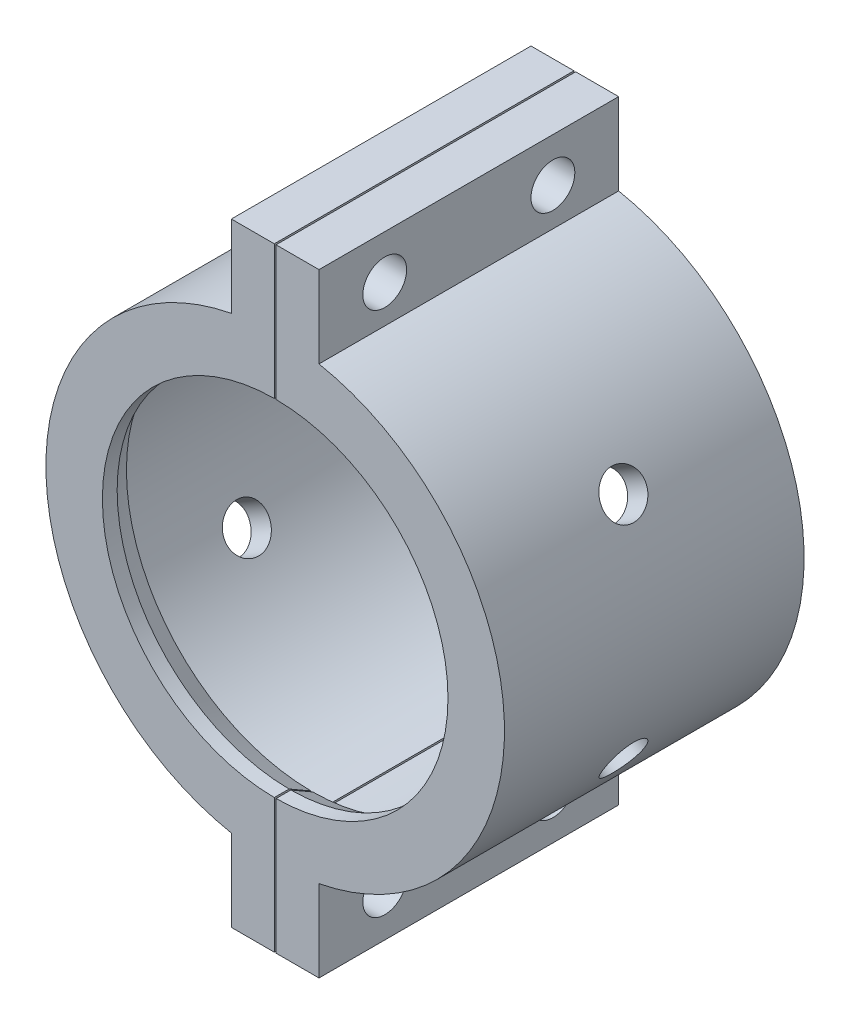
SolidWorks part; units mm, degrees
ref_plane "Front Plane" through (0, 0, 0) normal (0, 0, 1) x (1, 0, 0)
ref_plane "Top Plane" through (0, 0, 0) normal (0, 1, 0) x (1, 0, 0)
ref_plane "Right Plane" through (0, 0, 0) normal (1, 0, 0) x (0, 0, -1)
sketch "Sketch2" plane through (0, 0, 0) normal (0, 1, 0) x (1, 0, 0)
  line L0 (0, 0) -> (25.039, 0) construction
  line L1 (25.039, 0) -> (25.039, 2.14)
  line L2 (25.039, 2.14) -> (26.875, 5.32)
  line L3 (25.039, 2.14) -> (25.039, 5.32) construction
  line L4 (33.225, 5.32) -> (33.225, 0)
  line L5 (33.225, 0) -> (25.039, 0)
  line L6 (26.875, 5.32) -> (33.225, 5.32)
  line L7 (0, 0) -> (0, 46.1774) construction
  point P3 (0, 0)
  point P5 (0, 0)
  point P11 (0, 0)
  point P12 (0, 0)
  dimension "D2" = 26.875
  dimension "D3" = 5.32
  dimension "D4" = 3.18
  dimension "D5" = 6.35
  dimension "D6" = 30
revolve "Revolve1" add sketch "Sketch2" angle 360 about L7
sketch "Sketch8" plane through (0, 0, 0) normal (0, 1, 0) x (1, 0, 0)
  line L1 (-33.225, 5.32) -> (-33.225, 43.42)
  line L2 (-33.225, 43.42) -> (-29.845, 43.42)
  line L3 (-29.845, 43.42) -> (-29.845, 5.32)
  line L4 (33.225, 5.32) -> (-33.225, 5.32) construction
  line L5 (33.225, 5.32) -> (-33.225, 5.32) construction
  line L6 (-29.845, 5.32) -> (-33.225, 5.32)
  line L7 (0, 0) -> (0, 125.228) construction
  line L8 (-33.225, 0) -> (33.225, 0) construction
  dimension "D3" = 29.845
  dimension "D5" = 38.1
revolve "Revolve2" add sketch "Sketch8" angle 360 about L7
sketch "Sketch19" plane through (0, 0, 0) normal (0, 0, 1) x (1, 0, 0)
  line L0 (-6.35, 32.6125) -> (-6.35, 44.45)
  line L1 (6.35, -44.45) -> (-6.35, -44.45)
  line L2 (6.35, -44.45) -> (6.35, -32.6125)
  line L3 (6.35, 44.45) -> (-6.35, 44.45)
  line L4 (-6.35, -44.45) -> (-6.35, -32.6125)
  line L5 (6.35, -44.45) -> (-6.35, 44.45) construction
  line L6 (6.35, 44.45) -> (-6.35, -44.45) construction
  line L7 (6.35, 32.6125) -> (6.35, 44.45)
  circle A0 centre (0, 0) radius 33.225 construction
  arc A1 (-6.35, -32.6125) -> (6.35, -32.6125) centre (0, 0) ccw
  arc A2 (6.35, 32.6125) -> (-6.35, 32.6125) centre (0, 0) ccw
  dimension "D1" = 12.7
  dimension "D2" = 88.9
extrude "Boss-Extrude10" add sketch "Sketch19" against normal up to surface (43.42 mm away) up to face at (33.225, 0, -43.42)
sketch "Sketch18" plane through (0, 0, 0) normal (1, 0, 0) x (0, 0, -1)
  line L3 (43.42, 44.45) -> (0, 44.45) construction
  line L4 (0, -44.45) -> (0, -32.6125) construction
  line L5 (43.42, -32.6125) -> (43.42, -44.45) construction
  line L6 (43.42, -44.45) -> (0, -44.45) construction
  circle A0 centre (9.525, 38.1) radius 3.175
  circle A1 centre (33.895, 38.1) radius 3.175
  circle A2 centre (9.525, -38.1) radius 3.175
  circle A3 centre (33.895, -38.1) radius 3.175
  dimension "D1" = 6.35
  dimension "D2" = 6.35
  dimension "D3" = 9.525
  dimension "D4" = 9.525
  dimension "D5" = 6.35
extrude "Cut-Extrude7" cut sketch "Sketch18" against normal through all both and the other way through all
sketch "Sketch15" [suppressed] plane through (0, 0, -5.32) normal (0, 0, -1) x (-1, 0, 0)
  circle A1 centre (0, 0) radius 29.845
  circle A2 centre (0, 0) radius 29.845
  dimension "D1" = 0
sketch "Sketch21" plane through (0, 0, 0) normal (0, 0, 1) x (1, 0, 0)
  line L0 (0, 0) -> (0, 17.0984) construction
  line L1 (0, 0) -> (14.4923, 0) construction
  line L2 (0, 0) -> (14.7479, 8.5147) construction
  line L3 (-30.6026, 53.0053) -> (0, 0) construction
  line L4 (0, 0) -> (37.5938, 65.1143) construction
  dimension "D1" = 30
  dimension "D2" = 30
ref_axis "Axis4" through (0, 0, 3.175) along (0, 0, -1)
ref_plane "Plane1" through (0, 0, 0) normal (-0.866, -0.5, 0) x (-0.5, 0.866, 0)
sketch "Sketch23" plane through (0, 0, 0) normal (-0.866, -0.5, 0) x (-0.5, 0.866, 0)
  line L0 (0, -3.175) -> (0, 66.675) construction
  line L1 (0, 43.42) -> (0, 0) construction
  line L2 (33.225, 43.42) -> (-25.0683, 43.42) construction
  line L3 (-100000, 0) -> (100037.5938, 0) construction
  circle A0 centre (0, 21.71) radius 3.175
  point P13 (0, 21.71)
  dimension "D1" = 6.35
extrude "Cut-Extrude9" cut sketch "Sketch23" against normal through all both and the other way through all
mirror "Mirror3" about plane through (0, 0, 0) normal (0, 1, 0) of "Cut-Extrude9"
sketch "Sketch25" plane through (0, 0, 0) normal (0, 0, 1) x (1, 0, 0)
  line L1 (-0.127, -63.5) -> (0.127, -63.5)
  line L2 (-0.127, -63.5) -> (-0.127, 63.5)
  line L3 (-0.127, 63.5) -> (0.127, 63.5)
  line L4 (0.127, -63.5) -> (0.127, 63.5)
  line L5 (-0.127, -63.5) -> (0.127, 63.5) construction
  line L6 (-0.127, 63.5) -> (0.127, -63.5) construction
  point P0 (0, 0)
  dimension "D1" = 127
  dimension "D2" = 0.254
extrude "Cut-Extrude11" cut sketch "Sketch25" against normal through all both and the other way through all
extrude "Boss-Extrude6" [suppressed] add sketch "Sketch15" along normal up to surface (38.1 mm away)
sketch "Sketch12" [suppressed] plane through (0, 0, -63.5) normal (0, 0, -1) x (-1, 0, 0)
  line L1 (-12.7, 42.75) -> (12.7, 42.75)
  line L2 (-12.7, 42.75) -> (-12.7, 36.4)
  line L3 (-12.7, 36.4) -> (12.7, 36.4)
  line L4 (12.7, 42.75) -> (12.7, 36.4)
  line L5 (-12.7, 42.75) -> (12.7, 36.4) construction
  line L6 (-12.7, 36.4) -> (12.7, 42.75) construction
  circle A0 centre (0, 0) radius 39.575 construction
  point P0 (0, 39.575)
  dimension "D1" = 6.35
  dimension "D2" = 25.4
extrude "Boss-Extrude4" [suppressed] add sketch "Sketch12" against normal blind 25.4
sketch "Sketch11" [suppressed] plane through (0, 0, 0) normal (0, 1, 0) x (1, 0, 0)
  line L0 (29.845, 63.5) -> (-29.845, 63.5) construction
  line L1 (0, 44.4942) -> (5.461, 47.6471)
  line L2 (5.461, 47.6471) -> (5.461, 53.9529)
  line L3 (5.461, 53.9529) -> (0, 57.1058) construction
  line L4 (0, 57.1058) -> (-5.461, 53.9529) construction
  line L5 (-5.461, 53.9529) -> (-5.461, 47.6471)
  line L6 (-5.461, 47.6471) -> (0, 44.4942)
  line L7 (-5.461, 53.9529) -> (-5.715, 63.5)
  line L8 (39.575, 63.5) -> (-39.575, 63.5) construction
  line L9 (-5.715, 63.5) -> (5.715, 63.5)
  line L10 (5.715, 63.5) -> (5.461, 53.9529)
  circle A0 centre (0, 50.8) radius 5.461 construction
  point P19 (0, 63.5)
  dimension "D1" = 10.922
  dimension "D2" = 12.7
  dimension "D3" = 11.43
extrude "Cut-Extrude5" [suppressed] cut sketch "Sketch11" against normal blind 6.858 from offset 39.37
ref_axis "Axis1" through (0, 0, -66.675) along (0, 0, 1)
sketch "Sketch13" [suppressed] plane through (0, 0, 0) normal (0, 1, 0) x (1, 0, 0)
  line L0 (0, 66.675) -> (0, -3.175) construction
  line L1 (-12.7, 63.5) -> (12.7, 63.5) construction
  circle A0 centre (0, 50.8) radius 3.302
  dimension "D1" = 6.604
  dimension "D2" = 12.7
extrude "Cut-Extrude6" [suppressed] cut sketch "Sketch13" along normal through all
pattern_circular "CirPattern1" [suppressed] count 4 over 360 about axis through (0, 0, -66.675) along (0, 0, 1) of bodies 113
sketch "Sketch14" [suppressed] plane through (0, 0, -38.1) normal (0, 0, 1) x (1, 0, 0)
  line L3 (39.575, -12.7) -> (42.75, -12.7)
  line L4 (42.75, -12.7) -> (42.75, 12.7)
  line L5 (42.75, 12.7) -> (37.4819, 12.7)
  line L6 (39.575, -12.7) -> (42.75, -12.7)
  line L7 (42.75, -12.7) -> (42.75, 12.7)
  line L8 (42.75, 12.7) -> (37.4819, 12.7)
  line L9 (12.7, 37.4819) -> (12.7, 42.75)
  line L10 (12.7, 42.75) -> (-12.7, 42.75)
  line L11 (-12.7, 42.75) -> (-12.7, 37.4819)
  line L12 (12.7, 37.4819) -> (12.7, 42.75)
  line L13 (12.7, 42.75) -> (-12.7, 42.75)
  line L14 (-12.7, 42.75) -> (-12.7, 37.4819)
  line L15 (-37.4819, 12.7) -> (-42.75, 12.7)
  line L16 (-42.75, 12.7) -> (-42.75, -12.7)
  line L17 (-42.75, -12.7) -> (-39.575, -12.7)
  line L18 (-37.4819, 12.7) -> (-42.75, 12.7)
  line L19 (-42.75, 12.7) -> (-42.75, -12.7)
  line L20 (-42.75, -12.7) -> (-39.575, -12.7)
  line L22 (39.575, 0) -> (39.575, -12.7)
  line L23 (39.575, 0) -> (39.575, -12.7)
  line L24 (-39.575, -12.7) -> (-39.575, 0)
  line L25 (-39.575, -12.7) -> (-39.575, 0)
  arc A1 (39.575, 0) -> (37.4819, 12.7) centre (0, 0) ccw
  arc A2 (39.575, 0) -> (37.4819, 12.7) centre (0, 0) ccw
  arc A3 (12.7, 37.4819) -> (-12.7, 37.4819) centre (0, 0) ccw
  arc A4 (12.7, 37.4819) -> (-12.7, 37.4819) centre (0, 0) ccw
  arc A5 (-37.4819, 12.7) -> (-39.575, 0) centre (0, 0) ccw
  arc A6 (-37.4819, 12.7) -> (-39.575, 0) centre (0, 0) ccw
  dimension "D1" = 0
  dimension "D2" = 0
  dimension "D3" = 0
extrude "Boss-Extrude5" [suppressed] add sketch "Sketch14" along normal up to surface (38.1 mm away)
sketch "Sketch16" [suppressed] plane through (0, 0, -63.5) normal (0, 0, -1) x (-1, 0, 0)
  line L1 (42.75, -12.7) -> (39.575, -12.7)
  line L2 (42.75, -12.7) -> (42.75, -53.69)
  line L3 (42.75, -53.69) -> (39.575, -53.69)
  line L4 (39.575, -12.7) -> (39.575, -53.69)
  line L5 (-42.75, -12.7) -> (-39.575, -12.7)
  line L6 (-42.75, -12.7) -> (-42.75, -53.69)
  line L7 (-42.75, -53.69) -> (-39.575, -53.69)
  line L8 (-39.575, -12.7) -> (-39.575, -53.69)
extrude "Boss-Extrude7" [suppressed] add sketch "Sketch16" against normal up to surface (63.5 mm away)
sketch "Sketch17" [suppressed] plane through (0, 0, -63.5) normal (0, 0, -1) x (-1, 0, 0)
  line L0 (-42.75, 12.7) -> (-37.4819, 12.7)
  line L1 (37.4819, 12.7) -> (42.75, 12.7)
  line L2 (-12.7, 42.75) -> (-12.7, 37.4819)
  line L3 (12.7, 42.75) -> (12.7, 37.4819)
  arc A0 (42.75, 12.7) -> (12.7, 42.75) centre (0, 0) ccw
  arc A1 (37.4819, 12.7) -> (12.7, 37.4819) centre (0, 0) ccw
  arc A2 (-12.7, 42.75) -> (-42.75, 12.7) centre (0, 0) ccw
  arc A3 (-12.7, 37.4819) -> (-37.4819, 12.7) centre (0, 0) ccw
extrude "Boss-Extrude9" [suppressed] add sketch "Sketch17" against normal up to surface (63.5 mm away)
